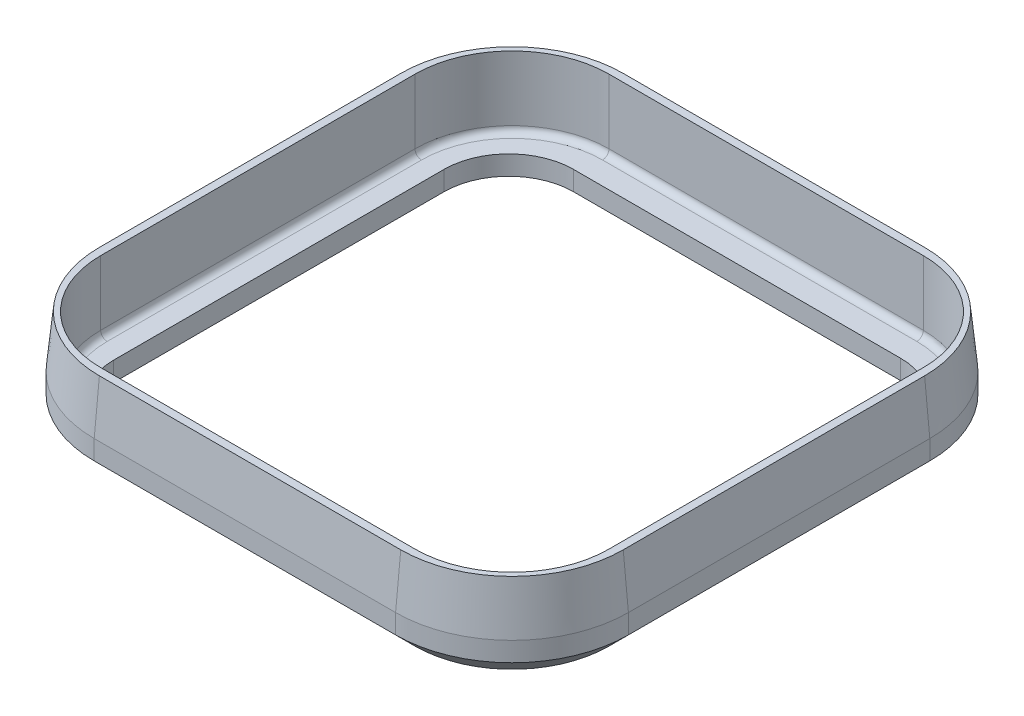
SolidWorks part; units mm, degrees
ref_plane "Front Plane" through (0, 0, 0) normal (0, 0, 1) x (1, 0, 0)
ref_plane "Top Plane" through (0, 0, 0) normal (0, 1, 0) x (1, 0, 0)
ref_plane "Right Plane" through (0, 0, 0) normal (1, 0, 0) x (0, 0, -1)
sketch "Sketch1" plane through (0, 0, 0) normal (0, 1, 0) x (1, 0, 0)
  line L0 (-29.8761, 33.4076) -> (22.1239, 33.4076)
  line L1 (-40.8761, 22.4076) -> (-40.8761, -29.5924)
  line L2 (-29.8761, -40.5924) -> (22.1239, -40.5924)
  line L3 (33.1239, 22.4076) -> (33.1239, -29.5924)
  line L4 (-30.3761, 30.9076) -> (22.6239, 30.9076)
  line L5 (-38.3761, 22.9076) -> (-38.3761, -30.0924)
  line L6 (-30.3761, -38.0924) -> (22.6239, -38.0924)
  line L7 (30.6239, 22.9076) -> (30.6239, -30.0924)
  line L8 (-30.1761, 33.7076) -> (22.4239, 33.7076)
  line L9 (-41.1761, 22.7076) -> (-41.1761, -29.8924)
  line L10 (-30.1761, -40.8924) -> (22.4239, -40.8924)
  line L11 (33.4239, 22.7076) -> (33.4239, -29.8924)
  line L12 (-28.1761, 35.7076) -> (20.4239, 35.7076)
  line L13 (-43.1761, 20.7076) -> (-43.1761, -27.8924)
  line L14 (-28.1761, -42.8924) -> (20.4239, -42.8924)
  line L15 (35.4239, 20.7076) -> (35.4239, -27.8924)
  line L17 (-27.1761, 37.7076) -> (19.4239, 37.7076)
  line L18 (-45.1761, 19.7076) -> (-45.1761, -26.8924)
  line L19 (-27.1761, -44.8924) -> (19.4239, -44.8924)
  line L20 (37.4239, 19.7076) -> (37.4239, -26.8924)
  arc A0 (22.6239, 30.9076) -> (30.6239, 22.9076) centre (22.6239, 22.9076) cw
  arc A1 (22.6239, -38.0924) -> (30.6239, -30.0924) centre (22.6239, -30.0924) ccw
  arc A2 (-38.3761, -30.0924) -> (-30.3761, -38.0924) centre (-30.3761, -30.0924) ccw
  arc A3 (-30.3761, 30.9076) -> (-38.3761, 22.9076) centre (-30.3761, 22.9076) ccw
  arc A4 (-40.8761, -29.5924) -> (-29.8761, -40.5924) centre (-29.8761, -29.5924) ccw
  arc A5 (22.1239, -40.5924) -> (33.1239, -29.5924) centre (22.1239, -29.5924) ccw
  arc A6 (22.1239, 33.4076) -> (33.1239, 22.4076) centre (22.1239, 22.4076) cw
  arc A7 (-29.8761, 33.4076) -> (-40.8761, 22.4076) centre (-29.8761, 22.4076) ccw
  arc A8 (-41.1761, -29.8924) -> (-30.1761, -40.8924) centre (-30.1761, -29.8924) ccw
  arc A9 (22.4239, -40.8924) -> (33.4239, -29.8924) centre (22.4239, -29.8924) ccw
  arc A10 (22.4239, 33.7076) -> (33.4239, 22.7076) centre (22.4239, 22.7076) cw
  arc A11 (-30.1761, 33.7076) -> (-41.1761, 22.7076) centre (-30.1761, 22.7076) ccw
  arc A12 (-43.1761, -27.8924) -> (-28.1761, -42.8924) centre (-28.1761, -27.8924) ccw
  arc A13 (20.4239, -42.8924) -> (35.4239, -27.8924) centre (20.4239, -27.8924) ccw
  arc A14 (20.4239, 35.7076) -> (35.4239, 20.7076) centre (20.4239, 20.7076) cw
  arc A15 (-28.1761, 35.7076) -> (-43.1761, 20.7076) centre (-28.1761, 20.7076) ccw
  arc A16 (-45.1761, -26.8924) -> (-27.1761, -44.8924) centre (-27.1761, -26.8924) ccw
  arc A17 (19.4239, -44.8924) -> (37.4239, -26.8924) centre (19.4239, -26.8924) ccw
  arc A18 (19.4239, 37.7076) -> (37.4239, 19.7076) centre (19.4239, 19.7076) cw
  arc A19 (-27.1761, 37.7076) -> (-45.1761, 19.7076) centre (-27.1761, 19.7076) ccw
  dimension "D5" = 8
  dimension "D6" = 11
  dimension "D11" = 11
  dimension "D16" = 15
  dimension "D21" = 18
  dimension "D1" = 2.5
  dimension "D2" = 2.5
  dimension "D3" = 2.5
  dimension "D4" = 2.5
  dimension "D7" = 0.3
  dimension "D8" = 0.3
  dimension "D9" = 0.3
  dimension "D10" = 0.3
  dimension "D12" = 2
  dimension "D13" = 2
  dimension "D14" = 2
  dimension "D15" = 2
  dimension "D17" = 2
  dimension "D18" = 2
  dimension "D19" = 2
  dimension "D20" = 2
extrude "Boss-Extrude1" add sketch "Sketch1" along normal blind 10 contours L17 A19 L18 A16 L19 A17 L20 A18 A15 L12 A14 L15 A13 L14 A12 L13 region at (-3.8761, 0, -36.5394)
extrude "Boss-Extrude2" add sketch "Sketch1<3>" along normal blind 2 contours L12 A15 L13 A12 L14 A13 L15 A14 A11 L8 A10 L11 A9 L10 A8 L9 region at (-3.8761, 0, -34.596)
sketch "Sketch1<3>" plane through (0, 0, 0) normal (0, 1, 0) x (1, 0, 0) same geometry as "Sketch1"
fillet "Fillet1" radius 1 8 edges at (-38.7827, 2, -31.3142) (-43.1761, 2, 3.5924) (-38.7827, 2, 38.4991) (-3.8761, 2, 42.8924) (31.0305, 2, 38.4991) (35.4239, 2, 3.5924) (31.0305, 2, -31.3142) (-3.8761, 2, -35.7076)
sketch "Sketch2" plane through (0, 10, 0) normal (0, 1, 0) x (1, 0, 0)
  line L0 (-28.1761, 35.7076) -> (20.4239, 35.7076) construction
  line L1 (35.4239, 20.7076) -> (35.4239, -27.8924) construction
  line L2 (-28.1761, -42.8924) -> (20.4239, -42.8924) construction
  line L3 (-43.1761, -27.8924) -> (-43.1761, 20.7076) construction
  line L4 (19.4239, 37.7076) -> (-27.1761, 37.7076)
  line L5 (-45.1761, 19.7076) -> (-45.1761, -26.8924)
  line L6 (-27.1761, -44.8924) -> (19.4239, -44.8924)
  line L7 (37.4239, -26.8924) -> (37.4239, 19.7076)
  line L8 (19.4239, 37.7076) -> (-27.1761, 37.7076)
  line L9 (-45.1761, 19.7076) -> (-45.1761, -26.8924)
  line L10 (-27.1761, -44.8924) -> (19.4239, -44.8924)
  line L11 (37.4239, -26.8924) -> (37.4239, 19.7076)
  line L12 (-28.1761, 35.7076) -> (20.4239, 35.7076)
  line L13 (35.4239, 20.7076) -> (35.4239, -27.8924)
  line L14 (-28.1761, -42.8924) -> (20.4239, -42.8924)
  line L15 (-43.1761, -27.8924) -> (-43.1761, 20.7076)
  arc A0 (-28.1761, 35.7076) -> (-43.1761, 20.7076) centre (-28.1761, 20.7076) ccw construction
  arc A1 (35.4239, 20.7076) -> (20.4239, 35.7076) centre (20.4239, 20.7076) ccw construction
  arc A2 (20.4239, -42.8924) -> (35.4239, -27.8924) centre (20.4239, -27.8924) ccw construction
  arc A3 (-43.1761, -27.8924) -> (-28.1761, -42.8924) centre (-28.1761, -27.8924) ccw construction
  arc A4 (-27.1761, 37.7076) -> (-45.1761, 19.7076) centre (-27.1761, 19.7076) ccw
  arc A5 (-45.1761, -26.8924) -> (-27.1761, -44.8924) centre (-27.1761, -26.8924) ccw
  arc A6 (19.4239, -44.8924) -> (37.4239, -26.8924) centre (19.4239, -26.8924) ccw
  arc A7 (37.4239, 19.7076) -> (19.4239, 37.7076) centre (19.4239, 19.7076) ccw
  arc A8 (-27.1761, 37.7076) -> (-45.1761, 19.7076) centre (-27.1761, 19.7076) ccw
  arc A9 (-45.1761, -26.8924) -> (-27.1761, -44.8924) centre (-27.1761, -26.8924) ccw
  arc A10 (19.4239, -44.8924) -> (37.4239, -26.8924) centre (19.4239, -26.8924) ccw
  arc A11 (37.4239, 19.7076) -> (19.4239, 37.7076) centre (19.4239, 19.7076) ccw
  arc A12 (-28.1761, 35.7076) -> (-43.1761, 20.7076) centre (-28.1761, 20.7076) ccw
  arc A13 (35.4239, 20.7076) -> (20.4239, 35.7076) centre (20.4239, 20.7076) ccw
  arc A14 (20.4239, -42.8924) -> (35.4239, -27.8924) centre (20.4239, -27.8924) ccw
  arc A15 (-43.1761, -27.8924) -> (-28.1761, -42.8924) centre (-28.1761, -27.8924) ccw
  dimension "D1" = 0
extrude "Boss-Extrude3" add sketch "Sketch2" along normal blind 3
chamfer "Chamfer2" distance 8 distance2 0.8 8 edges at (-45.1761, 13, 3.5924) (-39.904, 13, 39.6204) (-39.904, 13, -32.4355) (-3.8761, 13, 44.8924) (-3.8761, 13, -37.7076) (32.1519, 13, 39.6204) (32.1519, 13, -32.4355) (37.4239, 13, 3.5924) first distance on face at (-45.1761, 6.5, 3.5924) first distance on face at (-38.04, 6.5, 37.7564) first distance on face at (-38.04, 6.5, -30.5715) first distance on face at (-3.8761, 6.5, 44.8924) first distance on face at (-3.8761, 6.5, -37.7076) first distance on face at (30.2879, 6.5, 37.7564) first distance on face at (30.2879, 6.5, -30.5715) first distance on face at (37.4239, 6.5, 3.5924)
sketch "Sketch3" plane through (0, 0, 0) normal (0, -1, 0) x (1, 0, 0)
  line L0 (-30.1761, 40.8924) -> (22.4239, 40.8924) construction
  line L1 (-29.1761, -31.2076) -> (21.4239, -31.2076)
  line L2 (-39.1761, -21.2076) -> (-39.1761, 29.8924)
  line L3 (-29.1761, 39.8924) -> (21.4239, 39.8924)
  line L4 (31.4239, -21.2076) -> (31.4239, 29.8924)
  line L5 (33.4239, -22.7076) -> (33.4239, 29.8924) construction
  line L6 (-30.1761, -33.7076) -> (22.4239, -33.7076) construction
  line L7 (-41.1761, -22.7076) -> (-41.1761, 29.8924) construction
  line L8 (-30.1761, -33.7076) -> (22.4239, -33.7076)
  line L9 (33.4239, -22.7076) -> (33.4239, 29.8924)
  line L10 (-30.1761, 40.8924) -> (22.4239, 40.8924)
  line L11 (-41.1761, -22.7076) -> (-41.1761, 29.8924)
  arc A0 (-29.1761, -31.2076) -> (-39.1761, -21.2076) centre (-29.1761, -21.2076) cw
  arc A1 (21.4239, -31.2076) -> (31.4239, -21.2076) centre (21.4239, -21.2076) ccw
  arc A2 (21.4239, 39.8924) -> (31.4239, 29.8924) centre (21.4239, 29.8924) cw
  arc A3 (-39.1761, 29.8924) -> (-29.1761, 39.8924) centre (-29.1761, 29.8924) cw
  arc A4 (-41.1761, -22.7076) -> (-30.1761, -33.7076) centre (-30.1761, -22.7076) ccw construction
  arc A5 (22.4239, -33.7076) -> (33.4239, -22.7076) centre (22.4239, -22.7076) ccw construction
  arc A6 (33.4239, 29.8924) -> (22.4239, 40.8924) centre (22.4239, 29.8924) ccw construction
  arc A7 (-30.1761, 40.8924) -> (-41.1761, 29.8924) centre (-30.1761, 29.8924) ccw construction
  arc A8 (-41.1761, -22.7076) -> (-30.1761, -33.7076) centre (-30.1761, -22.7076) ccw
  arc A9 (22.4239, -33.7076) -> (33.4239, -22.7076) centre (22.4239, -22.7076) ccw
  arc A10 (33.4239, 29.8924) -> (22.4239, 40.8924) centre (22.4239, 29.8924) ccw
  arc A11 (-30.1761, 40.8924) -> (-41.1761, 29.8924) centre (-30.1761, 29.8924) ccw
  dimension "D5" = 10
  dimension "D1" = 1
  dimension "D2" = 2
  dimension "D3" = 2.5
  dimension "D4" = 2
extrude "Boss-Extrude4" add sketch "Sketch3" against normal up to vertex (2 mm away) up to point (22.4239, 2, -33.7076)
sketch "Sketch5" plane through (0, 0, 0) normal (0, -1, 0) x (1, 0, 0)
  line L4 (-39.1761, 29.8924) -> (-39.1761, -21.2076)
  line L5 (21.4239, 39.8924) -> (-29.1761, 39.8924)
  line L6 (31.4239, -21.2076) -> (31.4239, 29.8924)
  line L7 (-29.1761, -31.2076) -> (21.4239, -31.2076)
  line L8 (-39.1761, 29.8924) -> (-39.1761, -21.2076)
  line L9 (21.4239, 39.8924) -> (-29.1761, 39.8924)
  line L10 (31.4239, -21.2076) -> (31.4239, 29.8924)
  line L11 (-29.1761, -31.2076) -> (21.4239, -31.2076)
  line L12 (-27.1761, -37.7076) -> (19.4239, -37.7076)
  line L13 (37.4239, -19.7076) -> (37.4239, 26.8924)
  line L14 (19.4239, 44.8924) -> (-27.1761, 44.8924)
  line L15 (-45.1761, 26.8924) -> (-45.1761, -19.7076)
  line L16 (-27.1761, -37.7076) -> (19.4239, -37.7076)
  line L17 (37.4239, -19.7076) -> (37.4239, 26.8924)
  line L18 (19.4239, 44.8924) -> (-27.1761, 44.8924)
  line L19 (-45.1761, 26.8924) -> (-45.1761, -19.7076)
  arc A4 (-39.1761, -21.2076) -> (-29.1761, -31.2076) centre (-29.1761, -21.2076) ccw
  arc A5 (-29.1761, 39.8924) -> (-39.1761, 29.8924) centre (-29.1761, 29.8924) ccw
  arc A6 (31.4239, 29.8924) -> (21.4239, 39.8924) centre (21.4239, 29.8924) ccw
  arc A7 (21.4239, -31.2076) -> (31.4239, -21.2076) centre (21.4239, -21.2076) ccw
  arc A8 (-39.1761, -21.2076) -> (-29.1761, -31.2076) centre (-29.1761, -21.2076) ccw
  arc A9 (-29.1761, 39.8924) -> (-39.1761, 29.8924) centre (-29.1761, 29.8924) ccw
  arc A10 (31.4239, 29.8924) -> (21.4239, 39.8924) centre (21.4239, 29.8924) ccw
  arc A11 (21.4239, -31.2076) -> (31.4239, -21.2076) centre (21.4239, -21.2076) ccw
  arc A12 (19.4239, -37.7076) -> (37.4239, -19.7076) centre (19.4239, -19.7076) ccw
  arc A13 (37.4239, 26.8924) -> (19.4239, 44.8924) centre (19.4239, 26.8924) ccw
  arc A14 (-27.1761, 44.8924) -> (-45.1761, 26.8924) centre (-27.1761, 26.8924) ccw
  arc A15 (-45.1761, -19.7076) -> (-27.1761, -37.7076) centre (-27.1761, -19.7076) ccw
  arc A16 (19.4239, -37.7076) -> (37.4239, -19.7076) centre (19.4239, -19.7076) ccw
  arc A17 (37.4239, 26.8924) -> (19.4239, 44.8924) centre (19.4239, 26.8924) ccw
  arc A18 (-27.1761, 44.8924) -> (-45.1761, 26.8924) centre (-27.1761, 26.8924) ccw
  arc A19 (-45.1761, -19.7076) -> (-27.1761, -37.7076) centre (-27.1761, -19.7076) ccw
  dimension "D1" = 0
  dimension "D2" = 0
extrude "Boss-Extrude5" add sketch "Sketch5" along normal blind 1
chamfer "Chamfer3" distance 3 angle 45 8 edges at (-39.904, -1, 39.6204) (-45.1761, -1, 3.5924) (-3.8761, -1, 44.8924) (-39.904, -1, -32.4355) (32.1519, -1, 39.6204) (-3.8761, -1, -37.7076) (37.4239, -1, 3.5924) (32.1519, -1, -32.4355)
sketch "Sketch6" plane through (0, -1, 0) normal (0, -1, 0) x (1, 0, 0)
  line L1 (-14.8057, 39.8767) -> (7.1802, 39.8767)
  line L2 (-14.8057, 39.8767) -> (-14.8057, 40.1171)
  line L3 (-14.8057, 40.1171) -> (7.1802, 40.1171)
  line L4 (7.1802, 39.8767) -> (7.1802, 40.1171)
extrude "Cut-Extrude1" cut sketch "Sketch6" against normal blind 4
chamfer "Chamfer4" distance 2 angle 45 1 edges at (-3.8128, -1, 40.1171)
chamfer "Chamfer5" distance 1.5 angle 45 1 edges at (7.1802, -1, 40.8924)
chamfer "Chamfer6" distance 1.5 angle 45 1 edges at (-14.8057, -1, 40.8924)
